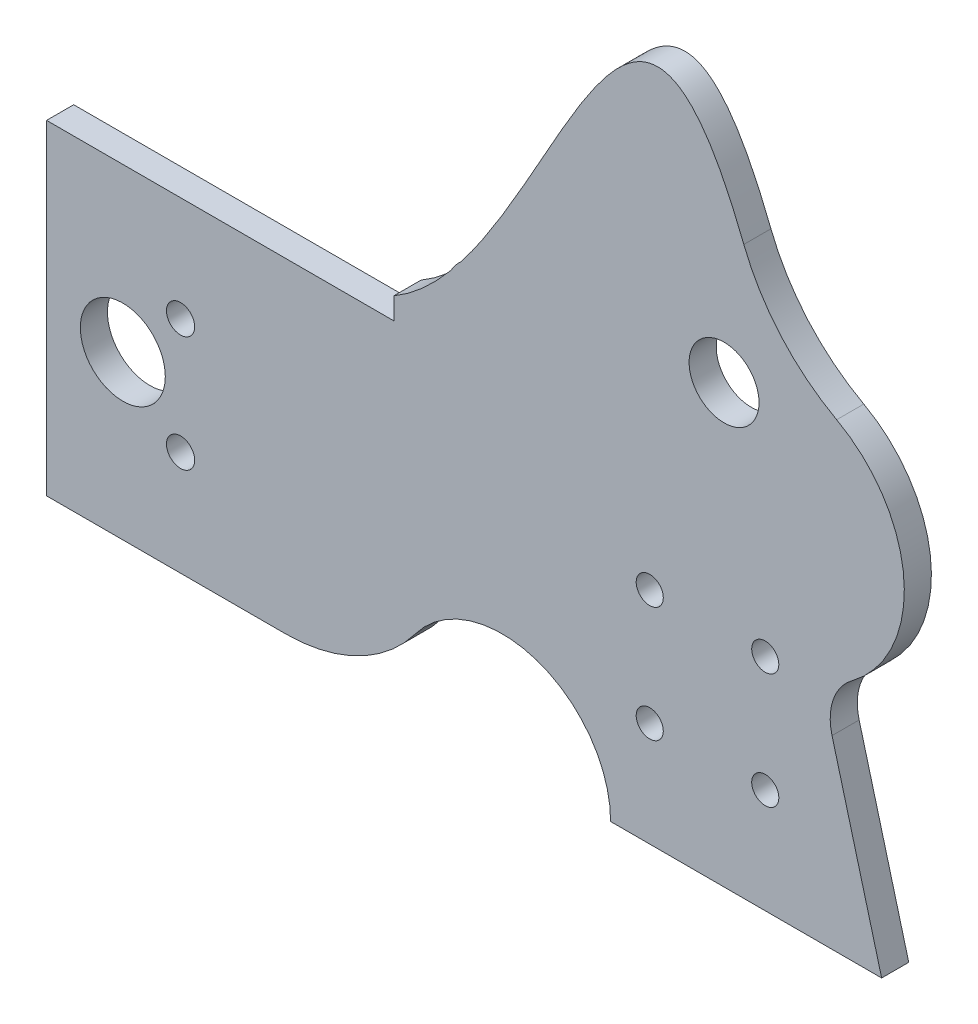
SolidWorks part; units mm, degrees
ref_plane "Front Plane" through (0, 0, 0) normal (0, 0, 1) x (1, 0, 0)
ref_plane "Top Plane" through (0, 0, 0) normal (0, 1, 0) x (1, 0, 0)
ref_plane "Right Plane" through (0, 0, 0) normal (1, 0, 0) x (0, 0, -1)
sketch "Sketch1" plane through (0, 0, 0) normal (0, 0, 1) x (1, 0, 0)
  line L0 (0, 0) -> (107.95, 0)
  line L3 (0, 38.1) -> (0, 25.4)
  line L4 (95.3675, 55.88) -> (0, 38.1)
  line L5 (0, 19.05) -> (100.2273, 19.05) construction
  line L6 (19.05, 19.05) -> (19.05, 28.62) construction
  line L7 (19.05, 19.05) -> (25.817, 25.817) construction
  line L8 (107.95, 0) -> (100.9363, 26.1756)
  line L10 (0, 12.7) -> (0, 0)
  line L11 (0, 25.4) -> (-7.62, 25.4)
  line L13 (0, 12.7) -> (-7.62, 12.7)
  line L14 (-7.62, 25.4) -> (-7.62, 12.7)
  line L15 (100.9363, 26.1756) -> (100.8688, 26.4276)
  arc A0 (100.8688, 26.4276) -> (95.3675, 55.88) centre (95.3675, 40.64) ccw
  circle A1 centre (95.3675, 40.64) radius 4.0957 construction
  circle A2 centre (19.05, 19.05) radius 9.57 construction
  circle A3 centre (25.817, 25.817) radius 1.651
  circle A4 centre (25.817, 12.283) radius 1.651
  circle A7 centre (12.283, 12.283) radius 1.651 [skipped]
  circle A8 centre (12.283, 25.817) radius 1.651 [skipped]
  point P26 (19.05, 19.05)
  dimension "D1" = 8.1915
  dimension "D5" = 15.24
  dimension "D4" = 19.14
  dimension "D7" = 3.302
  dimension "D11" = 97.0107
  dimension "D2" = 38.1
  dimension "D3" = 40.64
  dimension "D6" = 107.95
  dimension "D8" = 45
  dimension "D9" = 4
  dimension "D10" = 19.05
  dimension "D12" = 75
  dimension "D14" = 12.7
  dimension "D15" = 12.7
  dimension "D16" = 7.62
extrude "Boss-Extrude1" add sketch "Sketch1" along normal blind 3.175
sketch "Sketch2" plane through (0, 0, 3.175) normal (0, 0, 1) x (1, 0, 0)
  circle A0 centre (95.3675, 40.64) radius 38.1 construction
sketch "Sketch6" plane through (0, 0, 3.175) normal (0, 0, 1) x (1, 0, 0)
  line L0 (0, 0) -> (107.95, 0) construction
  line L1 (50.8, 0) -> (76.2, 0)
  arc A0 (76.2, 0) -> (50.8, 0) centre (63.5, 0) ccw
  dimension "D1" = 25.4
  dimension "D2" = 31.75
extrude "Cut-Extrude2" cut sketch "Sketch6" against normal blind 6.35
sketch "Sketch7" plane through (0, 0, 3.175) normal (0, 0, 1) x (1, 0, 0)
  line L0 (12.283, 25.817) -> (25.817, 12.283) construction
  line L1 (12.283, 12.283) -> (25.817, 25.817) construction
  circle A0 centre (19.05, 19.05) radius 4.9784
  circle A2 centre (80.7829, 12.2536) radius 1.5875
  circle A3 centre (94.316, 12.2536) radius 1.5875
  circle A4 centre (80.7829, 25.7876) radius 1.5875
  circle A5 centre (94.316, 25.7876) radius 1.5875
  dimension "D1" = 9.9568
extrude "Cut-Extrude3" cut sketch "Sketch7" against normal through all
fillet "Fillet1" radius 6.35 1 edges at (100.8688, 26.4276, 1.5875)
sketch "Sketch8" plane through (0, 0, 3.175) normal (0, 0, 1) x (1, 0, 0)
  line L1 (0, 38.1) -> (50.8, 38.1)
  line L2 (0, 38.1) -> (0, 50.8)
  line L3 (0, 50.8) -> (50.8, 50.8)
  line L4 (50.8, 38.1) -> (50.8, 50.8)
  dimension "D1" = 50.8
  dimension "D2" = 12.7
extrude "Cut-Extrude4" cut sketch "Sketch8" against normal blind 50.8
sketch "Sketch9" plane through (0, 0, 3.175) normal (0, 0, 1) x (1, 0, 0)
  line L3 (50.8, 40.64) -> (57.15, 40.64)
  line L5 (57.15, 40.64) -> (50.8, 40.64)
  line L6 (57.15, 40.64) -> (57.15, 50.8)
  line L7 (57.15, 50.8) -> (50.8, 50.8)
  line L8 (50.8, 40.64) -> (50.8, 50.8)
  line L9 (0, 38.1) -> (50.8, 38.1) construction
  line M8 (50.8, 47.571) -> (50.8, 38.1)
  line M21 (95.3675, 55.88) -> (50.8, 47.571)
  dimension "D1" = 10.16
  dimension "D2" = 2.54
  dimension "D3" = 6.35
extrude "Cut-Extrude5" cut sketch "Sketch9" against normal blind 19.304 contours L3 L6 M21 M8 region at (54.0583, 44.4092, 3.175)
fillet "Fillet6" radius 6.35 1 edges at (57.15, 40.64, 1.5875)
fillet "Fillet7" radius 6.35 1 edges at (57.15, 48.7549, 1.5875)
fillet "Fillet8" radius 19.05 1 edges at (50.8, 0, 1.5875)
sketch "Sketch12" plane through (0, 0, 3.175) normal (0, 0, 1) x (1, 0, 0)
  line L0 (107.95, 0) -> (146.812, 0) construction
  line L1 (8.0257, 45.4128) -> (80.6683, 75.7903) construction
  line L2 (95.3675, 40.64) -> (80.6683, 75.7903) construction
  line L3 (80.6683, 75.7903) -> (79.4434, 78.7195) construction
  line L4 (50.8, 40.64) -> (85.0271, 40.64)
  line L5 (85.0271, 40.64) -> (95.3675, 55.88)
  arc A0 (61.8128, 49.6242) -> (56.8883, 45.1859) centre (62.9766, 43.3817) ccw construction
  circle A1 centre (19.05, 19.05) radius 28.575 construction
  circle A2 centre (95.3675, 40.64) radius 38.1 construction
  circle A3 centre (80.6683, 75.7903) radius 3.175 construction
  spline S0 degree 3 poles (50.8, 40.64) (70.7778, 52.1788) (78.5943, 111.5434) (95.3675, 55.88) knots 0 0 0 0 1 1 1 1
  dimension "D2" = 6.35
  dimension "D1" = 38.862
extrude "Boss-Extrude2" add sketch "Sketch12" against normal blind 3.175
fillet "Fillet9" radius 24.13 1 edges at (95.3675, 55.88, 1.5875)
sketch "Sketch13" plane through (0, 38.1, 0) normal (0, 1, 0) x (1, 0, 0)
  line L0 (10.12, -3.175) -> (10.12, 0)
  line L1 (0, -3.175) -> (50.8, -3.175) construction
  line L2 (0, 0) -> (50.8, 0) construction
extrude "Cut-Extrude6" cut sketch "Sketch13" against normal through all
sketch "Sketch14" plane through (0, 0, 3.175) normal (0, 0, 1) x (1, 0, 0)
  circle A0 centre (89.49, 51.1876) radius 4.0958
  circle A1 centre (94.316, 25.7876) radius 1.5875 construction
  circle A2 centre (95.3675, 40.64) radius 4.0957 construction
  dimension "D1" = 4.826
  dimension "D2" = 25.4
extrude "Cut-Extrude7" cut sketch "Sketch14" against normal through all
